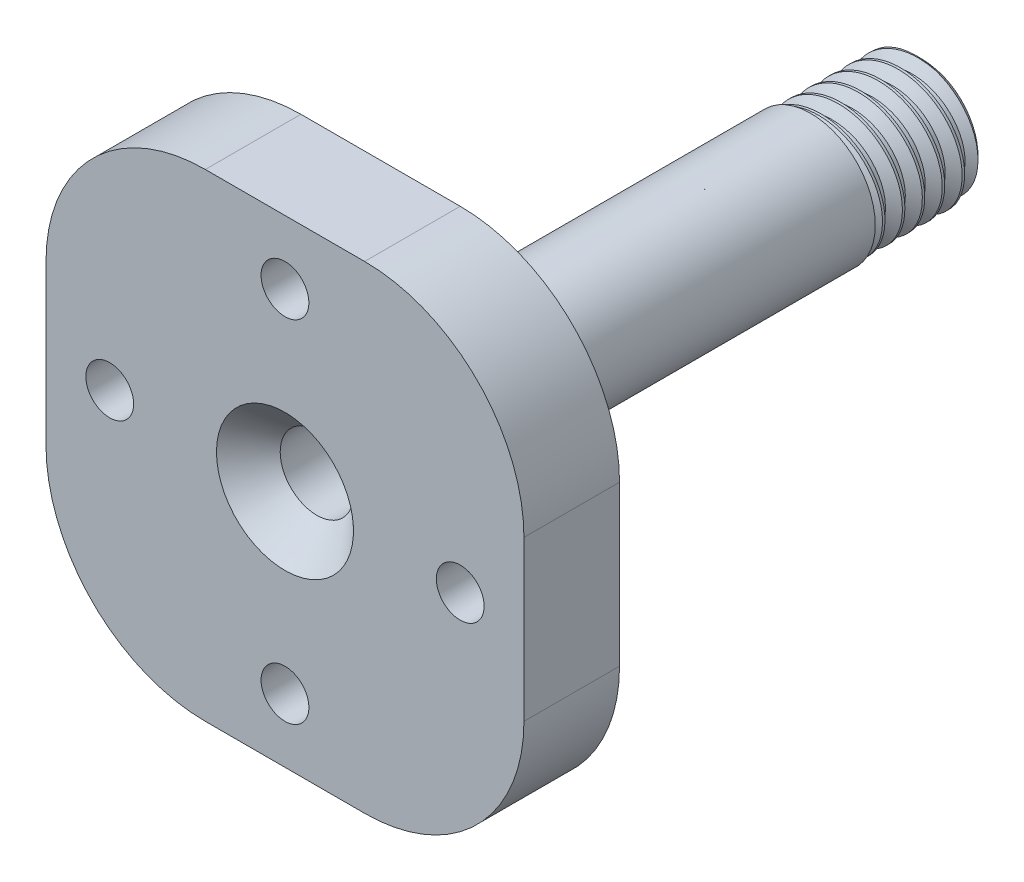
SolidWorks part; units mm, degrees
ref_plane "Alzado" through (0, 0, 0) normal (0, 0, 1) x (1, 0, 0)
ref_plane "Planta" through (0, 0, 0) normal (0, 1, 0) x (1, 0, 0)
ref_plane "Vista lateral" through (0, 0, 0) normal (1, 0, 0) x (0, 0, -1)
sketch "Croquis1" plane through (0, 0, 0) normal (0, 0, 1) x (1, 0, 0)
  circle A0 centre (0, 0) radius 3.9
  circle A23 centre (-0.4495, 0.5219) radius 0.5
  circle A24 centre (0.6209, 0.3005) radius 0.5
  circle A30 centre (0.707, 1.5431) radius 0.5
  circle A37 centre (-0.4495, 1.6293) radius 0.5
  circle A38 centre (-1.4584, 0.9649) radius 0.5
  circle A39 centre (1.6298, 0.8461) radius 0.5
  circle A45 centre (-1.6798, -0.4992) radius 0.5
  circle A46 centre (-0.917, -1.4466) radius 0.5
  circle A47 centre (0.2641, -1.7173) radius 0.5
  circle A48 centre (1.6298, -0.3762) radius 0.5
  circle A96 centre (0, 0) radius 2.3
  dimension "D1" = 7.8
  dimension "D2" = 1.6
extrude "Saliente-Extruir1" add sketch "Croquis1" against normal blind 7 contours A0
chamfer "Chaflán2" distance 0.4 angle 45 1 edges at (3.9, 0, -7)
thread "Rosca1" pitch 1.25 method cut profile "Perfil de rosca1" start angle 0, offset 1.5, length 9, pitch 1.25, diameter 7.8
ref_plane "Plano1" through (3.9, 0, -8.1) normal (0, -1, 0) x (1, 0, 0)
sketch "Perfil de rosca1" plane through (3.9, 0, -8.1) normal (0, -1, 0) x (1, 0, 0)
  line L0 (0, 0) -> (0, 1.25) construction
  line L11 (0, 0) -> (0, 1.0937)
  line L12 (0, 1.0937) -> (-0.6766, 0.7031)
  line L13 (-0.6766, 0.7031) -> (-0.6766, 0.3906)
  line L15 (-0.6766, 0.3906) -> (0, 0)
  line L17 (-0.6766, 0.5469) -> (0, 0.5469) construction
  point P2 (0, 0)
  dimension "Pitch" = 1.25
  dimension "Profile_Angle" = 60
  dimension "Profile_Land" = 0.3125
  dimension "Profile_Height" = 0.6766
sketch "Croquis20" plane through (0, 0, 0) normal (0, 0, 1) x (1, 0, 0)
  circle A0 centre (0, 0) radius 4.05
  dimension "D1" = 8.1
extrude "Saliente-Extruir2" add sketch "Croquis20" along normal blind 25 contours A0
sketch "Croquis21" plane through (0, 0, 25) normal (0, 0, 1) x (1, 0, 0)
  circle A0 centre (0, 0) radius 5.5
  dimension "D1" = 11
extrude "Saliente-Extruir3" add sketch "Croquis21" along normal blind 2
sketch "Croquis23" plane through (0, 0, 27) normal (0, 0, 1) x (1, 0, 0)
  line L0 (-15, 0) -> (15, 0) construction
  line L1 (-15, -15) -> (15, -15)
  line L2 (-15, -15) -> (-15, 15)
  line L3 (-15, 15) -> (15, 15)
  line L4 (15, -15) -> (15, 15)
  line L7 (0, -15) -> (0, 15) construction
  circle A0 centre (-11, 0) radius 1.5
  circle A1 centre (11, 0) radius 1.5
  circle A2 centre (0, -11) radius 1.5
  circle A3 centre (0, 11) radius 1.5
  point P0 (0, 0)
  point P14 (0, 0)
  point P15 (0, 0)
  point P20 (0, 0)
  point P21 (0, -9.2226)
  point P22 (0, 9.8175)
  dimension "D3" = 3
  dimension "D1" = 30
  dimension "D2" = 30
  dimension "D5" = 4
  dimension "D4" = 4
extrude "Saliente-Extruir4" add sketch "Croquis23" along normal blind 6
chamfer "Chaflán3" distance 2 angle 45 1 edges at (5.5, 0, 27)
sketch "Croquis24" plane through (0, 0, 27) normal (0, 0, -1) x (-1, 0, 0)
  circle A0 centre (11, 0) radius 3.5
  circle A1 centre (0, -11) radius 3.5
  circle A2 centre (-11, 0) radius 3.5
  circle A3 centre (0, 11) radius 3.5
  dimension "D1" = 7
extrude "Cortar-Extruir2" cut sketch "Croquis24" against normal blind 3
extrude "Cortar-Extruir1" cut sketch "Croquis1<3>" against normal through all both and the other way through all contours A96
sketch "Croquis1<3>" plane through (0, 0, 0) normal (0, 0, 1) x (1, 0, 0) same geometry as "Croquis1"
chamfer "Chaflán4" distance 2 angle 45 1 edges at (2.3, 0, 33)
fillet "Redondeo1" radius 10 4 edges at (-15, -15, 30) (15, -15, 30) (-15, 15, 30) (15, 15, 30)
equation "\"D1@Croquis1\" = \"dmax\""
equation "\"pitch\"= 1.25"
equation "\"h\"= 0.866 * \"pitch\""
equation "\"dmax\"= 7.8"
equation "\"dpitch\"= \"dmax\" - 0.649519"
equation "\"dmin\"= \"dmax\" - 1.082532"
equation "\"angle_pressure\"= 60"
equation "\"axis_len\"= 25"
equation "\"D1@Saliente-Extruir2\"=\"axis_len\""
equation "\"D1@Croquis21\"=8+3"
equation "\"D2@Croquis23\"=\"D1@Croquis23\""
equation "\"D4@Croquis23\"=\"D5@Croquis23\""
equation "\"D1@Saliente-Extruir4\"=3+3"
